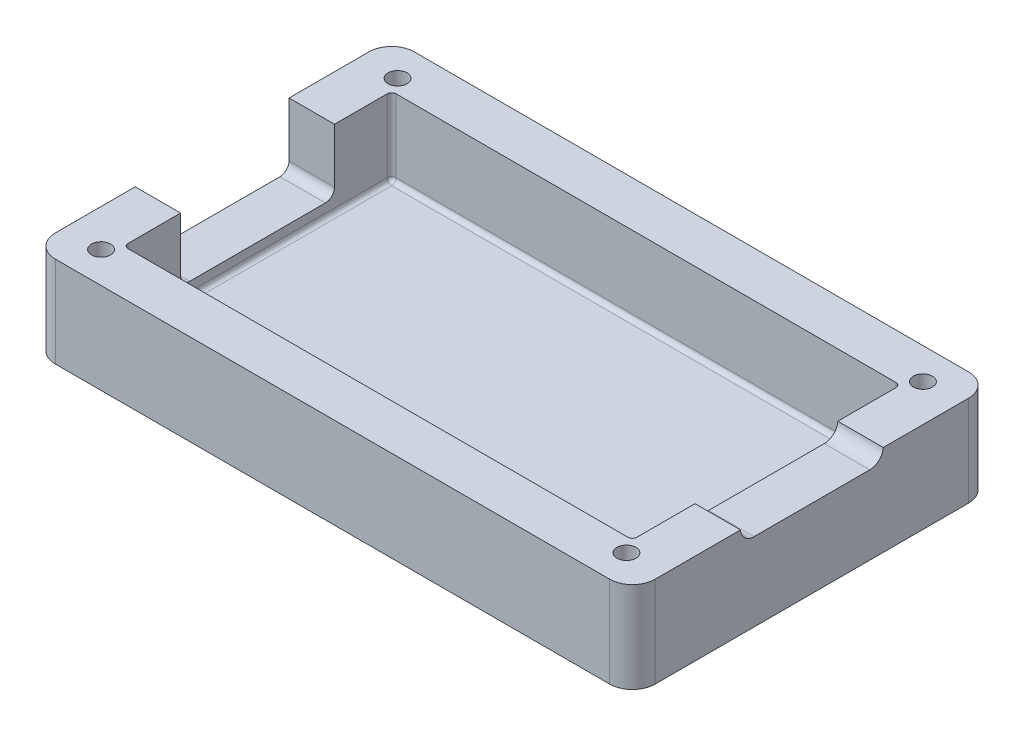
SolidWorks part; units mm, degrees
ref_plane "Front Plane" through (0, 0, 0) normal (0, 0, 1) x (1, 0, 0)
ref_plane "Top Plane" through (0, 0, 0) normal (0, 1, 0) x (1, 0, 0)
ref_plane "Right Plane" through (0, 0, 0) normal (1, 0, 0) x (0, 0, -1)
sketch "Sketch1" plane through (0, 0, 0) normal (0, 1, 0) x (1, 0, 0)
  line L0 (59.4693, 3.9968) -> (59.4693, -13.5292) construction
  line L1 (59.4693, 5.2668) -> (25.9413, 5.2668)
  line L2 (59.4693, 5.2668) -> (59.4693, -14.7992)
  line L3 (59.4693, -14.7992) -> (25.9413, -14.7992)
  line L4 (25.9413, 5.2668) -> (25.9413, -14.7992)
  line L5 (59.4693, 5.2668) -> (25.9413, -14.7992) construction
  line L6 (59.4693, -14.7992) -> (25.9413, 5.2668) construction
  line L7 (27.2113, 5.2668) -> (58.1993, 5.2668) construction
  line L8 (25.9413, -13.5292) -> (25.9413, 3.9968) construction
  line L9 (58.1993, -14.7992) -> (27.2113, -14.7992) construction
  point P0 (0, 0)
extrude "Boss-Extrude1" add sketch "Sketch1" along normal blind 5.08
sketch "Sketch3" plane through (0, 5.08, 0) normal (0, 1, 0) x (1, 0, 0)
  line L1 (56.9293, -12.2592) -> (28.4813, -12.2592)
  line L2 (56.9293, -12.2592) -> (56.9293, 2.7268)
  line L3 (56.9293, 2.7268) -> (28.4813, 2.7268)
  line L4 (28.4813, -12.2592) -> (28.4813, 2.7268)
  line L5 (56.9293, -12.2592) -> (28.4813, 2.7268) construction
  line L6 (56.9293, 2.7268) -> (28.4813, -12.2592) construction
  line L8 (56.9293, 2.4728) -> (56.9293, -0.7748) construction
  line L9 (28.7353, 2.7268) -> (56.6753, 2.7268) construction
  line L10 (56.6753, -12.2592) -> (28.7353, -12.2592) construction
  line L11 (28.4813, -12.0052) -> (28.4813, -9.0657) construction
  point P0 (0, 0)
extrude "Cut-Extrude1" cut sketch "Sketch3" against normal blind 4.318
sketch "Sketch4" plane through (0, 5.08, 0) normal (0, 1, 0) x (1, 0, 0)
  circle A0 centre (57.3892, 3.5209) radius 0.5309
  circle A1 centre (57.3892, -13.0532) radius 0.5309
  circle A2 centre (28.0214, -13.0532) radius 0.5309
  circle A3 centre (28.0214, 3.5209) radius 0.5309
  circle A4 centre (57.3892, 3.5209) radius 0.5309 construction
  circle A5 centre (57.3892, -13.0532) radius 0.5309 construction
  circle A6 centre (28.0214, -13.0532) radius 0.5309 construction
  circle A8 centre (28.0214, 3.5209) radius 0.5309 construction
extrude "Cut-Extrude2" cut sketch "Sketch4" against normal blind 4.318
fillet "Fillet1" radius 1.27 4 edges at (25.9413, 2.54, -5.2668) (59.4693, 2.54, -5.2668) (25.9413, 2.54, 14.7992) (59.4693, 2.54, 14.7992)
fillet "Fillet2" radius 0.254 4 edges at (56.9293, 2.921, -2.7268) (56.9293, 2.921, 12.2592) (28.4813, 2.921, 12.2592) (28.4813, 2.921, -2.7268)
fillet "Fillet3" radius 0.254 8 edges at (56.8549, 0.762, 12.1848) (42.7053, 0.762, 12.2592) (28.5557, 0.762, 12.1848) (28.4813, 0.762, 4.7662) (28.5557, 0.762, -2.6524) (42.7053, 0.762, -2.7268) (56.8549, 0.762, -2.6524) (56.9293, 0.762, 4.7662)
sketch "Sketch5" plane through (25.9413, 0, 0) normal (-1, 0, 0) x (0, 0, 1)
  line L0 (-3.9968, 5.08) -> (13.5292, 5.08) construction
  line L1 (9.0657, 5.08) -> (0.4666, 5.08)
  line L2 (9.0657, 5.08) -> (9.0657, 1.5218)
  line L3 (9.0657, 1.5218) -> (0.4666, 1.5218)
  line L4 (0.4666, 5.08) -> (0.4666, 1.5218)
  line L5 (-3.9968, 0) -> (13.5292, 0) construction
  line L6 (0.4666, 7.0062) -> (0.4666, 5.08) construction
  point P8 (4.7662, 5.08)
  point P9 (4.7662, 0)
extrude "Cut-Extrude3" cut sketch "Sketch5" against normal up to next
fillet "Fillet4" radius 0.508 2 edges at (27.2113, 1.5218, 0.4666) (27.2113, 1.5218, 9.0657)
ref_plane "Plane1" through (56.6753, 0.762, -2.4728) normal (0, 0, -1) x (-1, 0, 0)
sketch "Sketch7" plane through (59.4693, 0, 0) normal (1, 0, 0) x (0, 0, -1)
  line L0 (3.9968, 5.08) -> (-0.7748, 5.08) construction
  line L1 (-0.7748, 5.08) -> (-8.7576, 5.08)
  line L2 (-0.7748, 5.08) -> (-0.7748, 4.3755)
  line L3 (-0.7748, 4.3755) -> (-8.7576, 4.3755)
  line L4 (-8.7576, 5.08) -> (-8.7576, 4.3755)
  line L5 (-13.5292, 0) -> (3.9968, 0) construction
  point P6 (-4.7662, 4.3755)
  point P9 (-4.7662, 0)
  point P11 (0, 0)
extrude "Cut-Extrude4" cut sketch "Sketch7" against normal up to next
fillet "Fillet5" radius 0.762 2 edges at (58.1993, 4.3755, 8.7576) (58.1993, 4.3755, 0.7748)
